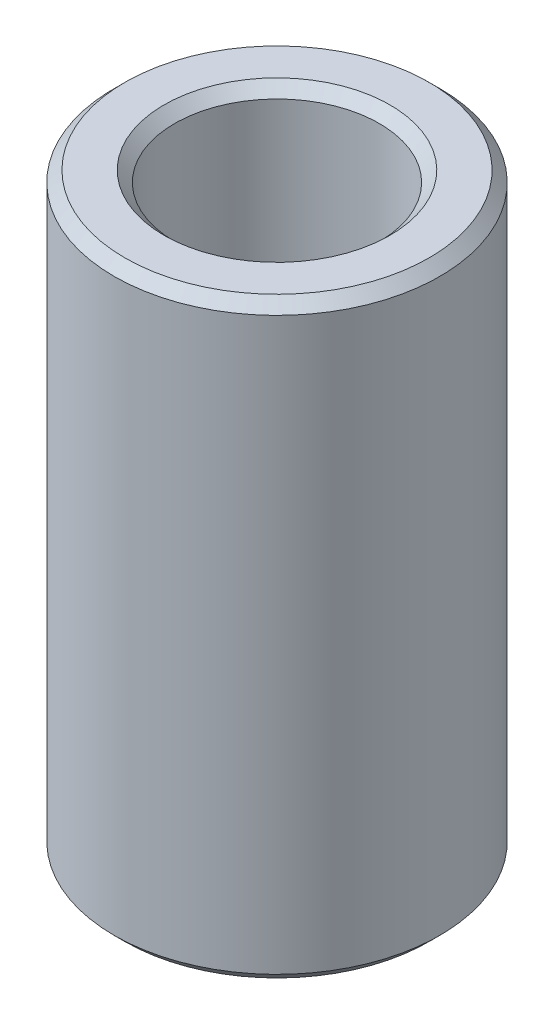
SolidWorks part; units mm, degrees
ref_plane "Front Plane" through (0, 0, 0) normal (0, 0, 1) x (1, 0, 0)
ref_plane "Top Plane" through (0, 0, 0) normal (0, 1, 0) x (1, 0, 0)
ref_plane "Right Plane" through (0, 0, 0) normal (1, 0, 0) x (0, 0, -1)
sketch "Sketch1" plane through (0, 0, 0) normal (0, 1, 0) x (1, 0, 0)
  circle A0 centre (0, 0) radius 35
  dimension "SLEEVE_OD" = 70
extrude "Boss-Extrude1" add sketch "Sketch1" along normal blind 127.3004
sketch "Sketch2" plane through (0, 0, 0) normal (0, 1, 0) x (1, 0, 0)
  circle A0 centre (0, 0) radius 21.9924
  dimension "BORE_D" = 43.9849
extrude "Cut-Extrude1" cut sketch "Sketch2" along normal through all
chamfer "Chamfer1" distance 2.3023 angle 45 4 edges at (0, 127.3004, 21.9924) (0, 0, 21.9924) (0, 0, 35) (0, 127.3004, 35)
